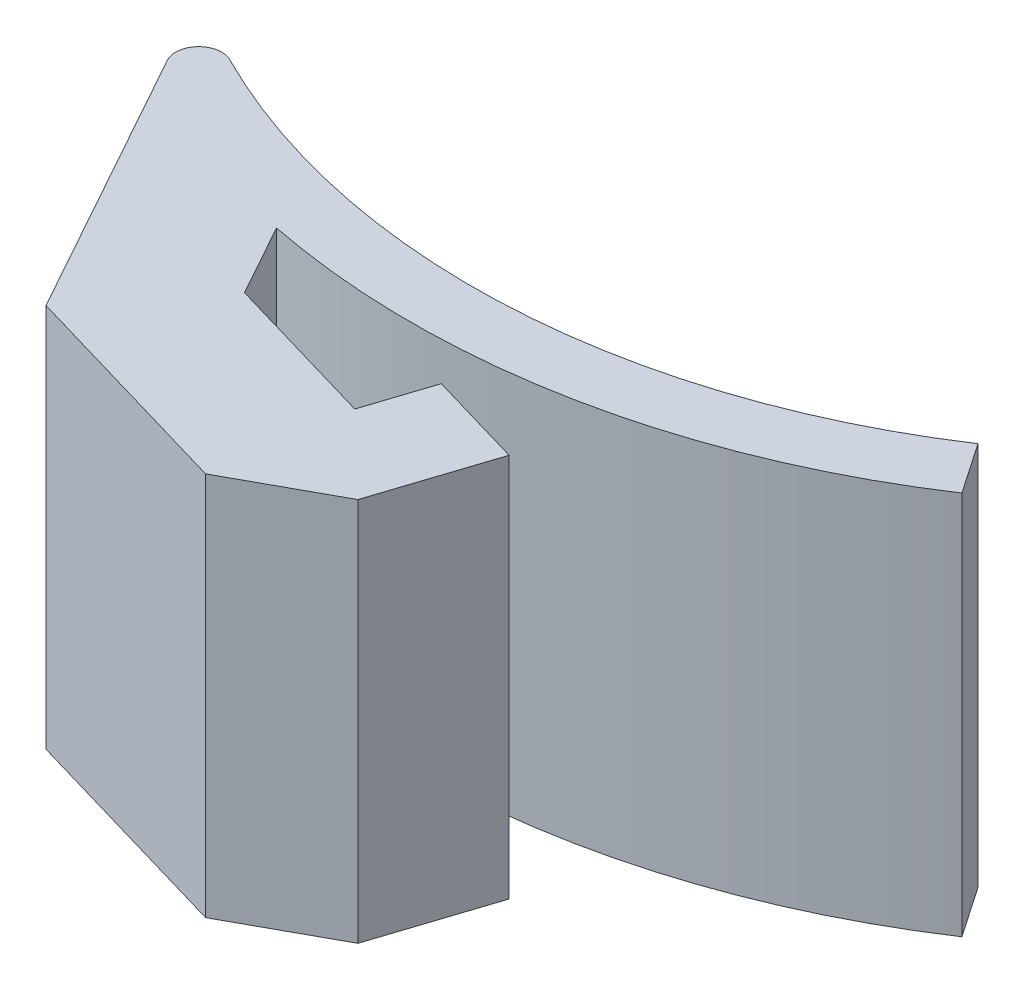
SolidWorks part; units mm, degrees
ref_plane "Спереди" through (0, 0, 0) normal (0, 0, 1) x (1, 0, 0)
ref_plane "Сверху" through (0, 0, 0) normal (0, 1, 0) x (1, 0, 0)
ref_plane "Справа" through (0, 0, 0) normal (1, 0, 0) x (0, 0, -1)
sketch "Эскиз1" plane through (0, 0, 0) normal (0, 1, 0) x (1, 0, 0)
  line L0 (4.2452, -5.0108) -> (4.7271, -3.3642) construction
  line L1 (2.5, -4.5) -> (6.3951, -5.64)
  line L2 (6.3951, -5.64) -> (7.2, -3.175)
  line L3 (7.2, -3.175) -> (5.9523, -2.8099)
  line L4 (5.9523, -2.8099) -> (5.6754, -3.658)
  line L5 (5.6754, -3.658) -> (3.6472, -3.0644)
  line L6 (3.6472, -3.0644) -> (3.1268, -2.1278)
  line L7 (10.12, 0.0055) -> (10.5711, -0.6553)
  line L9 (0.5267, -0.9481) -> (2.5, -4.5)
  line L10 (2.1224, -3.8203) -> (3.5998, -2.9995) construction
  arc A0 (0.9239, -0.5345) -> (10.12, 0.0055) centre (5.0558, 7.6737) ccw
  arc A1 (3.1268, -2.1278) -> (10.5711, -0.6553) centre (5.0558, 7.6737) ccw
  arc A3 (-0.4009, -0.6938) -> (10.5609, -0.6621) centre (5.0558, 7.6737) ccw construction
  arc A4 (0.0361, -0.0237) -> (10.12, 0.0055) centre (5.0558, 7.6737) ccw construction
  arc A5 (0.9239, -0.5345) -> (0.5267, -0.9481) centre (0.789, -0.8024) ccw
  point P12 (3.1251, -2.9116)
  point P14 (3.6084, -2.9947)
  point P18 (5.5945, -1.5)
  point P25 (4.7228, -3.3792)
  point P26 (0, 0)
  point P27 (0.7605, -0.5038)
  dimension "D8" = 0.3
  dimension "D1" = 10.12
  dimension "D2" = 1.7
  dimension "D3" = 4.5
  dimension "D4" = 2.5
  dimension "D5" = 7.2
  dimension "D6" = 5.64
  dimension "D7" = 1.3
  dimension "D9" = 1.7
  dimension "D11" = 1.5
  dimension "D12" = 0.8
extrude "Бобышка-Вытянуть1" add sketch "Эскиз1" along normal blind 5
chamfer "Фаска1" distance 1 angle 45 1 edges at (6.3951, 2.5, 5.64) first distance on face at (4.4475, 2.5, 5.07)
